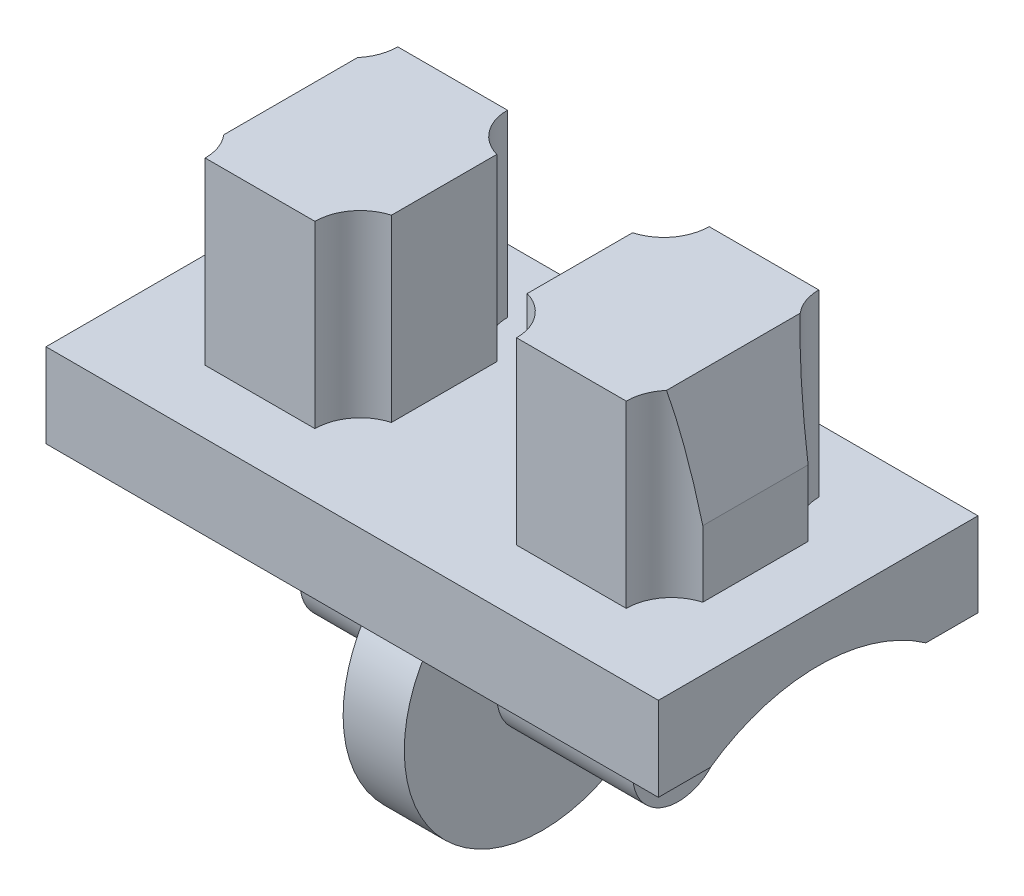
SolidWorks part; units mm, degrees
ref_plane "Front Plane" through (0, 0, 0) normal (0, 0, 1) x (1, 0, 0)
ref_plane "Top Plane" through (0, 0, 0) normal (0, 1, 0) x (1, 0, 0)
ref_plane "Right Plane" through (0, 0, 0) normal (1, 0, 0) x (0, 0, -1)
sketch "Sketch1" plane through (0, 0, 0) normal (1, 0, 0) x (0, 0, -1)
  line L0 (0, 0) -> (0, 4.8671) construction
  line L1 (-2.73, 2.7371) -> (-2.73, 2.1982)
  line L2 (2.73, 2.7371) -> (2.73, 2.1982)
  line L3 (-4.05, 2.7371) -> (-2.73, 2.7371)
  line L4 (-4.05, 2.7371) -> (-4.05, 4.8671)
  line L5 (-4.05, 4.8671) -> (4.05, 4.8671)
  line L6 (2.73, 2.7371) -> (4.05, 2.7371)
  line L7 (4.05, 2.7371) -> (4.05, 4.8671)
  arc A0 (-2.73, 2.1982) -> (2.73, 2.1982) centre (0, 0) ccw
  circle A2 centre (0, 0) radius 1.155
  arc A3 (-2.73, 2.7371) -> (2.73, 2.7371) centre (0, -1.15) cw
  point P13 (0, -0.4861)
  point P14 (0, -0.7056)
  dimension "D1" = 3.505
  dimension "D3" = 4.75
  dimension "D6" = 2.31
  dimension "D7" = 1.15
  dimension "D2" = 5.46
  dimension "D4" = 2.13
  dimension "D5" = 4.05
extrude "Boss-Extrude1" add sketch "Sketch1" along normal blind 4.215 contours A2 region at (0, 0, 0)
extrude "Boss-Extrude2" add sketch "Sketch1<3>" along normal blind 0.775 contours A2 L1 A0 L2 region at (0, 3.5002, 0)
sketch "Sketch1<3>" plane through (0, 0, 0) normal (1, 0, 0) x (0, 0, -1) same geometry as "Sketch1"
extrude "Boss-Extrude3" add sketch "Sketch1<4>" along normal blind 7.76 contours L0 L5 L4 L3 | L0 L6 L7 L5 region at (0, 3.9656, 2.2501) region at (0, 3.9656, -2.2501)
sketch "Sketch1<4>" plane through (0, 0, 0) normal (1, 0, 0) x (0, 0, -1) same geometry as "Sketch1"
sketch "Sketch2" plane through (0, 4.8671, 0) normal (0, 1, 0) x (1, 0, 0)
  line L0 (0, 0) -> (7.76, 0) construction
  line L1 (0, -4.05) -> (0, 4.05) construction
  line L2 (7.76, -4.05) -> (7.76, 4.05) construction
  line L3 (1.72, -1.334) -> (1.72, 1.334)
  line L4 (2.555, 2.44) -> (5.335, 2.44)
  line L5 (6.17, 1.334) -> (6.17, -1.334)
  line L6 (3.945, 2.44) -> (3.945, 0) construction
  line L7 (2.555, -2.44) -> (5.335, -2.44)
  arc A0 (1.72, 1.334) -> (2.555, 2.44) centre (1.405, 2.44) ccw
  arc A1 (6.17, 1.334) -> (5.335, 2.44) centre (6.485, 2.44) cw
  arc A2 (6.17, -1.334) -> (5.335, -2.44) centre (6.485, -2.44) ccw
  arc A3 (1.72, -1.334) -> (2.555, -2.44) centre (1.405, -2.44) cw
  point P14 (3.8797, 0)
  point P15 (4.1985, 2.44)
  point P16 (3.945, 2.44)
  point P17 (0, 0)
  point P20 (3.88, 0)
  point P21 (3.945, -0.424)
  point P22 (0, 0)
  point P24 (6.17, 0)
  point P29 (1.72, 0)
  dimension "D4" = 1.15
  dimension "D1" = 4.45
  dimension "D2" = 1.59
  dimension "D3" = 2.44
  dimension "D5" = 2.54
extrude "Boss-Extrude4" add sketch "Sketch2" along normal blind 4.55
chamfer "Chamfer1" distance 2.87 distance2 0.56 1 edges at (6.17, 9.4171, 0) first distance on face at (6.17, 7.1421, 0)
mirror "Mirror1" about plane through (0, 0, 0) normal (1, 0, 0) of bodies 104
